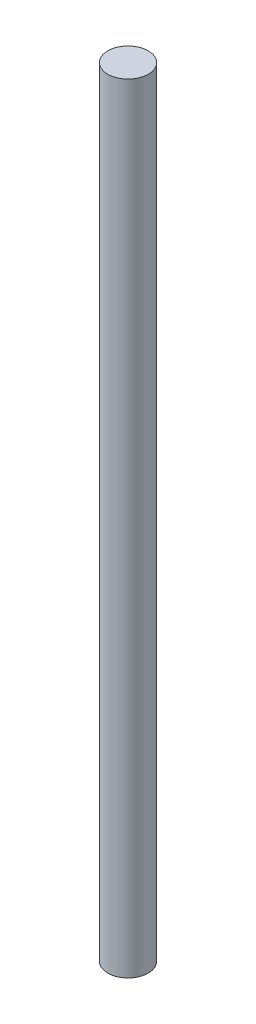
SolidWorks part; units mm, degrees
ref_plane "Front Plane" through (0, 0, 0) normal (0, 0, 1) x (1, 0, 0)
ref_plane "Top Plane" through (0, 0, 0) normal (0, 1, 0) x (1, 0, 0)
ref_plane "Right Plane" through (0, 0, 0) normal (1, 0, 0) x (0, 0, -1)
sketch "Sketch1" plane through (0, 0, 0) normal (0, 1, 0) x (1, 0, 0)
  circle A0 centre (0, 0) radius 3.9688
extrude "Boss-Extrude1" add sketch "Sketch1" along normal blind 152.4
